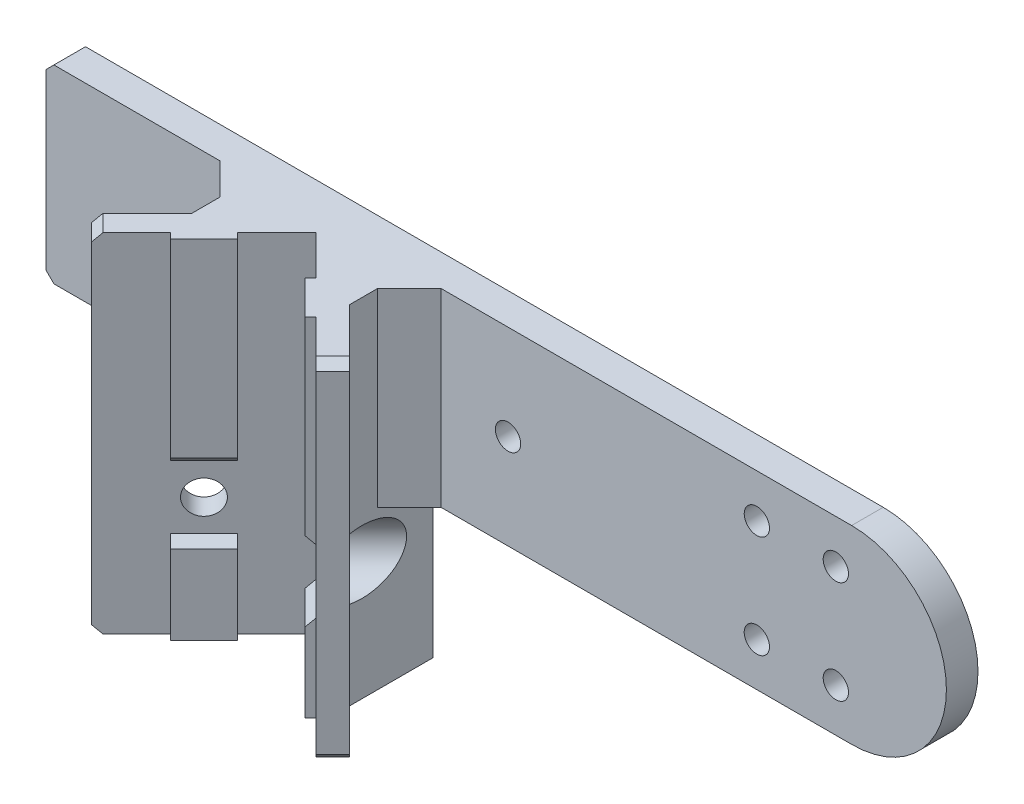
SolidWorks part; units mm, degrees
ref_plane "Alzado" through (0, 0, 0) normal (0, 0, 1) x (1, 0, 0)
ref_plane "Planta" through (0, 0, 0) normal (0, 1, 0) x (1, 0, 0)
ref_plane "Vista lateral" through (0, 0, 0) normal (1, 0, 0) x (0, 0, -1)
sketch "Croquis1" plane through (0, 0, 0) normal (0, 0, 1) x (1, 0, 0)
  line L0 (0, 0) -> (0, 18835.1574) construction
  line L1 (0, 0) -> (-18835.1574, 0) construction
  line L2 (10, -12) -> (36, -12)
  line L3 (-36, -12) -> (36, -12) construction
  line L4 (-36, -12) -> (-36, 12)
  line L5 (-36, 12) -> (36, 12)
  line L6 (36, -12) -> (36, 12)
  line L7 (-36, -12) -> (36, 12) construction
  line L8 (-36, 12) -> (36, -12) construction
  line L9 (-17.5, 6) -> (17.5, 6) construction
  line L10 (-17.5, 6) -> (-17.5, -6) construction
  line L11 (-17.5, -6) -> (17.5, -6) construction
  line L12 (17.5, 6) -> (17.5, -6) construction
  line L13 (-17.5, 6) -> (17.5, -6) construction
  line L14 (-17.5, -6) -> (17.5, 6) construction
  line L15 (-10, -32) -> (10, -32)
  line L16 (-10, -32) -> (-10, -12)
  line L17 (-10, -12) -> (10, -12) construction
  line L18 (10, -32) -> (10, -12)
  line L19 (-10, -32) -> (10, -12) construction
  line L20 (-10, -12) -> (10, -32) construction
  line L21 (-36, -12) -> (-10, -12)
  circle A0 centre (-22.5, 0) radius 1.6
  circle A1 centre (22.5, 0) radius 1.6
  point P7 (0, 0)
  point P12 (0, -22)
  point P16 (0, 0)
  dimension "D1" = 3.2
  dimension "D2" = 45
  dimension "D3" = 24
  dimension "D4" = 13.5
  dimension "D5" = 35
  dimension "D6" = 12
  dimension "D7" = 20
  dimension "D8" = 20
extrude "Saliente-Extruir1" add sketch "Croquis1" along normal blind 4
sketch "Croquis3" plane through (0, 0, 0) normal (0, 0, -1) x (-1, 0, 0)
  line L0 (0, 0) -> (-50000, 0) construction
  line L1 (-66, 12) -> (-36, 12)
  line L2 (-66, -12) -> (-36, -12)
  line L3 (-36, -12) -> (-36, 12)
  line L4 (-36, -12) -> (-36, 12) construction
  arc A0 (-66, 12) -> (-66, -12) centre (-66, 0) ccw
  circle A1 centre (-54, 6.5) radius 1.6
  circle A2 centre (-64, 6.5) radius 1.6
  circle A3 centre (-54, -6.5) radius 1.6
  circle A4 centre (-64, -6.5) radius 1.6
  dimension "D1" = 30
  dimension "D2" = 3.2
  dimension "D5" = 28
  dimension "D3" = 13
  dimension "D4" = 18
extrude "Saliente-Extruir3" add sketch "Croquis3" against normal blind 4
sketch "Croquis5" plane through (0, 12, 0) normal (0, 1, 0) x (1, 0, 0)
  line L0 (0, 0) -> (0, 50000) construction
  line L1 (-10, -11.5445) -> (-10, -4)
  line L2 (66, -4) -> (-36, -4) construction
  line L5 (66, 0) -> (-36, 0) construction
  line L7 (0, -34.2128) -> (14.2128, -20) construction
  line L8 (0, -34.2128) -> (-14.2128, -20) construction
  line L9 (-14.2128, -20) -> (0, -5.7872) construction
  line L10 (14.2128, -20) -> (0, -5.7872) construction
  line L11 (0, -34.2128) -> (0, -5.7872) construction
  line L12 (-14.2128, -20) -> (14.2128, -20) construction
  line L13 (16.449, -17.9935) -> (0, -1.5445) construction
  line L14 (0, -1.5445) -> (-16.3342, -17.8787) construction
  line L15 (-16.3342, -17.8787) -> (-14.2128, -20)
  line L16 (-16.3342, -17.8787) -> (-10, -11.5445)
  line L18 (0, -20) -> (-7.1064, -12.8936) construction
  line L19 (0, -20) -> (7.1064, -12.8936) construction
  line L20 (-8.5206, -15.722) -> (-4.278, -11.4794)
  line L21 (-4.278, -11.4794) -> (-4.9851, -10.7723)
  line L22 (-8.5206, -15.722) -> (-9.2277, -15.0149)
  line L23 (-9.2277, -15.0149) -> (-14.2128, -20)
  line L24 (0, -5.7872) -> (-4.9851, -10.7723)
  line L25 (-10, -4) -> (10, -4)
  line L26 (0, -20) -> (7.1064, -12.8936) construction
  line L27 (0, -1.5445) -> (16.3342, -17.8787) construction
  line L28 (14.2128, -20) -> (0, -5.7872) construction
  line L29 (0, -5.7872) -> (4.9851, -10.7723)
  line L30 (9.2277, -15.0149) -> (14.2128, -20)
  line L31 (8.5206, -15.722) -> (9.2277, -15.0149)
  line L32 (4.278, -11.4794) -> (4.9851, -10.7723)
  line L33 (8.5206, -15.722) -> (4.278, -11.4794)
  line L34 (16.3342, -17.8787) -> (10, -11.5445)
  line L35 (16.3342, -17.8787) -> (14.2128, -20)
  line L36 (10, -11.5445) -> (10, -4)
  point P3 (0, -20)
  point P25 (0, -4)
  dimension "D1" = 20.1
  dimension "D2" = 45
  dimension "D3" = 1
  dimension "D4" = 20
  dimension "D5" = 20
  dimension "D6" = 6
  dimension "D7" = 3
extrude "Saliente-Extruir4" add sketch "Croquis5" against normal through all
sketch "Croquis6" plane through (0, -32, 0) normal (0, -1, 0) x (1, 0, 0)
  line L0 (-10, 0) -> (10, 0) construction
  line L1 (0, 0) -> (0, 50000) construction
  line L2 (-4.4882, 0) -> (-7.4882, 0)
  line L3 (-3, 4.5) -> (3, 4.5)
  line L4 (-2.9544, 1.4996) -> (2.9544, 1.4996)
  line L6 (7.4882, 0) -> (4.4882, 0)
  arc A0 (-4.4882, 0) -> (-2.9544, 1.4996) centre (-2.9882, 0) cw
  arc A1 (-7.4882, 0) -> (-3, 4.5) centre (-2.9882, 0) cw
  arc A2 (7.4882, 0) -> (3, 4.5) centre (2.9882, 0) ccw
  arc A3 (4.4882, 0) -> (2.9544, 1.4996) centre (2.9882, 0) ccw
  point P12 (0, 4.5)
  point P18 (0, 1.4996)
  dimension "D1" = 3
  dimension "D2" = 1.5
  dimension "D3" = 3
extrude "Cortar-Extruir1" cut sketch "Croquis6" against normal blind 4 from offset 2 offset against normal yes
pattern_linear "MatrizL1" count 2 spacing 10 along (0, 1, 0) of "Cortar-Extruir1"
sketch "Croquis7" plane through (0.7723, 0, 0.7723) normal (-0.7071, 0, -0.7071) x (-0.7071, 0, 0.7071)
  line L0 (14.1421, -45.7417) -> (14.1421, 49954.2583) construction
  line L1 (24.1921, -32) -> (24.1921, 12) construction
  line L2 (15.2343, -32) -> (24.1921, -32) construction
  circle A0 centre (14.1421, -17) radius 2.1
  dimension "D2" = 4.2
  dimension "D1" = 10.05
  dimension "D3" = 15
extrude "Cortar-Extruir2" cut sketch "Croquis7" against normal through all both and the other way through all
sketch "Croquis8" plane through (0.7723, 0, 0.7723) normal (-0.7071, 0, -0.7071) x (-0.7071, 0, 0.7071)
  circle A0 centre (14.1421, -17) radius 4
  dimension "D1" = 8
extrude "Cortar-Extruir3" cut sketch "Croquis8" along normal through all
sketch "Croquis9" plane through (-0.7723, 0, 0.7723) normal (0.7071, 0, -0.7071) x (-0.7071, 0, -0.7071)
  line L0 (-14.1421, -44.0861) -> (-14.1421, 49955.9139) construction
  line L1 (-24.1921, -32) -> (-24.1921, 12) construction
  line L2 (-15.2343, -32) -> (-7.0711, -32) construction
  circle A0 centre (-14.1421, -17) radius 2.1
  dimension "D2" = 4.2
  dimension "D1" = 10.05
  dimension "D3" = 15
extrude "Cortar-Extruir4" cut sketch "Croquis9" against normal through all both and the other way through all
sketch "Croquis10" plane through (-0.7723, 0, 0.7723) normal (0.7071, 0, -0.7071) x (-0.7071, 0, -0.7071)
  circle A0 centre (-14.1421, -17) radius 4
  dimension "D1" = 8
extrude "Cortar-Extruir5" cut sketch "Croquis10" along normal through all
chamfer "Chaflán1" distance 4 angle 45 2 edges at (-10, 0, 4) (10, 0, 4)
chamfer "Chaflán2" distance 1 angle 45 9 edges at (15.2735, 12, 18.9393) (15.2735, -32, 18.9393) (-15.2735, 12, 18.9393) (-15.2735, -32, 18.9393) (-36, 12, 2) (-36, -12, 2) (10, -22, 0) (-10, -22, 0) (0, -32, 0)
sketch "Croquis11" plane through (-3.6007, 0, 3.6007) normal (-0.7071, 0, 0.7071) x (0.7071, 0, 0.7071)
  line L0 (17.1421, -32) -> (17.1421, 12) construction
  line L1 (11.1421, -21) -> (17.1421, -21)
  line L2 (11.1421, -21) -> (11.1421, -13)
  line L3 (11.1421, -13) -> (17.1421, -13)
  line L4 (17.1421, -21) -> (17.1421, -13)
  line L5 (11.1421, -21) -> (17.1421, -13) construction
  line L6 (11.1421, -13) -> (17.1421, -21) construction
  point P0 (14.1421, -17)
  dimension "D1" = 8
extrude "Cortar-Extruir6" cut sketch "Croquis11" against normal up to surface (1 mm away) up to face at (12.3154, -10, 18.1026)
sketch "Croquis12" plane through (3.6007, 0, 3.6007) normal (0.7071, 0, 0.7071) x (0.7071, 0, -0.7071)
  line L0 (-11.1421, -32) -> (-11.1421, 12) construction
  line L1 (-17.1421, -13) -> (-11.1421, -13)
  line L2 (-17.1421, -13) -> (-17.1421, -21)
  line L3 (-17.1421, -21) -> (-11.1421, -21)
  line L4 (-11.1421, -13) -> (-11.1421, -21)
  line L5 (-17.1421, -13) -> (-11.1421, -21) construction
  line L6 (-17.1421, -21) -> (-11.1421, -13) construction
  point P0 (-14.1421, -17)
  dimension "D1" = 8
extrude "Cortar-Extruir7" cut sketch "Croquis12" against normal up to surface (1 mm away) up to face at (-12.3154, -10, 18.1026)
chamfer "Chaflán3" distance 1 angle 45 4 edges at (-6.3993, -21, 13.6007) (6.3993, -21, 13.6007) (6.3993, -13, 13.6007) (-6.3993, -13, 13.6007)
